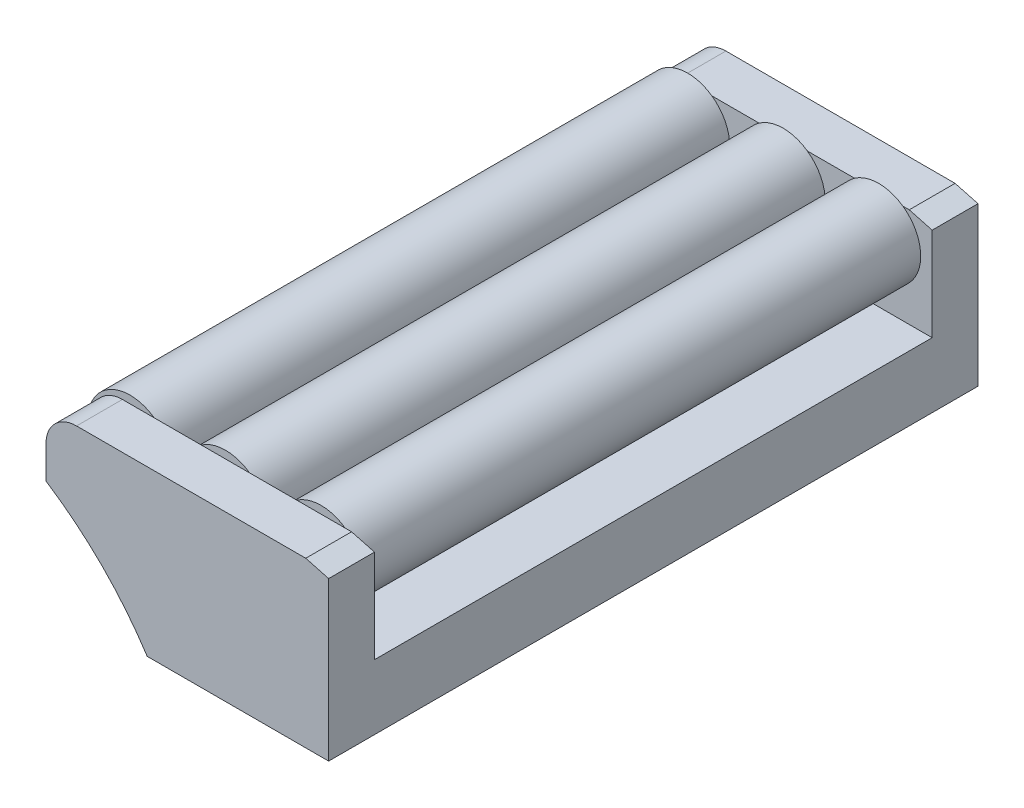
SolidWorks part; units mm, degrees
ref_plane "Frontale" through (0, 0, 0) normal (0, 0, 1) x (1, 0, 0)
ref_plane "Superiore" through (0, 0, 0) normal (0, 1, 0) x (1, 0, 0)
ref_plane "Destro" through (0, 0, 0) normal (1, 0, 0) x (0, 0, -1)
sketch "Schizzo1" plane through (0, 0, 0) normal (0, 0, 1) x (1, 0, 0)
  line L1 (0, 0) -> (37, 0)
  line L2 (0, 0) -> (0, 21.5)
  line L3 (0, 21.5) -> (37, 21.5)
  line L4 (37, 0) -> (37, 21.5)
  dimension "D1" = 37
  dimension "D2" = 21.5
extrude "Estrusione1" add sketch "Schizzo1" along normal blind 85
sketch "Schizzo6" plane through (37, 0, 0) normal (1, 0, 0) x (0, 0, -1)
  line L1 (-85, 0) -> (-85, 21.5) construction
  line L2 (-85, 0) -> (0, 0) construction
  line L9 (-79, 32.1395) -> (-6, 32.1395)
  line L10 (-79, 32.1395) -> (-79, 8.5)
  line L11 (-79, 8.5) -> (-6, 8.5)
  line L12 (-6, 32.1395) -> (-6, 8.5)
  line L13 (-317.5773, 8.5) -> (13.8875, 8.5) construction
  dimension "D1" = 6
  dimension "D2" = 8.5
  dimension "D5" = 6
extrude "Taglio-Estrusione4" cut sketch "Schizzo6" against normal blind 84
sketch "Schizzo7" plane through (0, 0, 6) normal (0, 0, 1) x (1, 0, 0)
  line L0 (-1.4369, 17) -> (39.1559, 17) construction
  line L1 (0, 21.5) -> (0, 0) construction
  line L4 (-9.1685, 22.5) -> (40.6482, 22.5) construction
  circle A0 centre (5, 17) radius 5.5
  circle A1 centre (17.5, 17) radius 5.5
  circle A2 centre (30, 17) radius 5.5
  dimension "D1" = 11
  dimension "D2" = 11
  dimension "D3" = 11
  dimension "D4" = 12.5
  dimension "D5" = 12.5
  dimension "D6" = 5
  dimension "D7" = 17
extrude "Estrusione4" add sketch "Schizzo7" along normal up to surface (73 mm away) up to face at (18.5, 15, 79)
chamfer "Smusso1" distance 3 angle 15 2 edges at (37, 21.5, 3) (37, 21.5, 82) first distance on face at (17.9, 21.5, 4.8) first distance on face at (17.9, 21.5, 80.2)
fillet "Raccordo1" radius 4 2 edges at (0, 21.5, 82) (0, 21.5, 3)
sketch "Schizzo8" plane through (0, 0, 85) normal (0, 0, 1) x (1, 0, 0)
  line L0 (13, 34.4094) -> (13, -14.7843) construction
  line L1 (-11.3793, 13) -> (48.784, 13) construction
  line L2 (0, 0) -> (37, 0) construction
  line L3 (13, 13) -> (-36.0671, -36.0671) construction
  circle A0 centre (-24.5, -24.5) radius 45
  dimension "D4" = 90
  dimension "D1" = 13
  dimension "D2" = 13
  dimension "D3" = 45
  dimension "D5" = 37.5
extrude "Taglio-Estrusione5" cut sketch "Schizzo8" against normal through all
sketch "Schizzo9" plane through (0, 0, 0) normal (0, -1, 0) x (1, 0, 0)
  line L0 (13.2459, 85) -> (37, 85) construction
  line L1 (23, 127.0005) -> (23, -20.4205) construction
  line L4 (37, 85) -> (37, 0) construction
  circle A0 centre (23, 75.5) radius 3
  circle A1 centre (23, 9.5) radius 3
  dimension "D1" = 6
  dimension "D2" = 6
  dimension "D3" = 66
  dimension "D4" = 9.5
  dimension "D5" = 14
extrude "Taglio-Estrusione6" cut sketch "Schizzo9" against normal up to surface (8.5 mm away) up to face at (21.5471, 8.5, 42.5)
